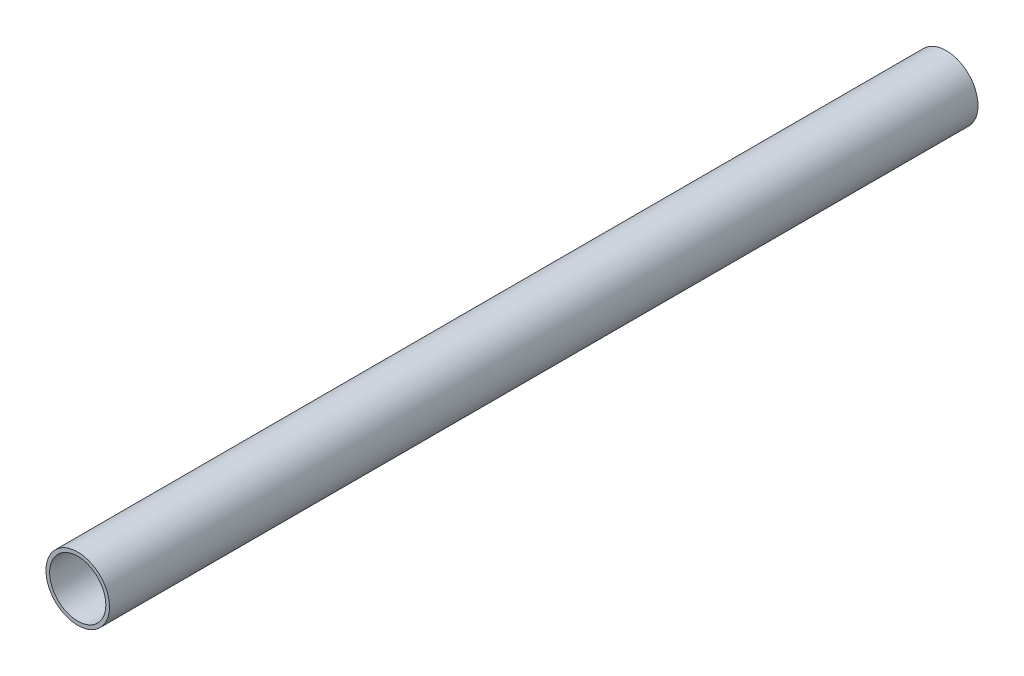
SolidWorks part; units mm, degrees
material "Thornel Mat VMA"
ref_plane "Front Plane" through (0, 0, 0) normal (0, 0, 1) x (1, 0, 0)
ref_plane "Top Plane" through (0, 0, 0) normal (0, 1, 0) x (1, 0, 0)
ref_plane "Right Plane" through (0, 0, 0) normal (1, 0, 0) x (0, 0, -1)
sketch "Sketch1" plane through (0, 0, 0) normal (0, 0, 1) x (1, 0, 0)
  circle A0 centre (0, 0) radius 6.5
  circle A1 centre (0, 0) radius 5.75
  dimension "D1" = 13
  dimension "D2" = 11.5
extrude "Boss-Extrude1" add sketch "Sketch1" along normal blind 177.6501
